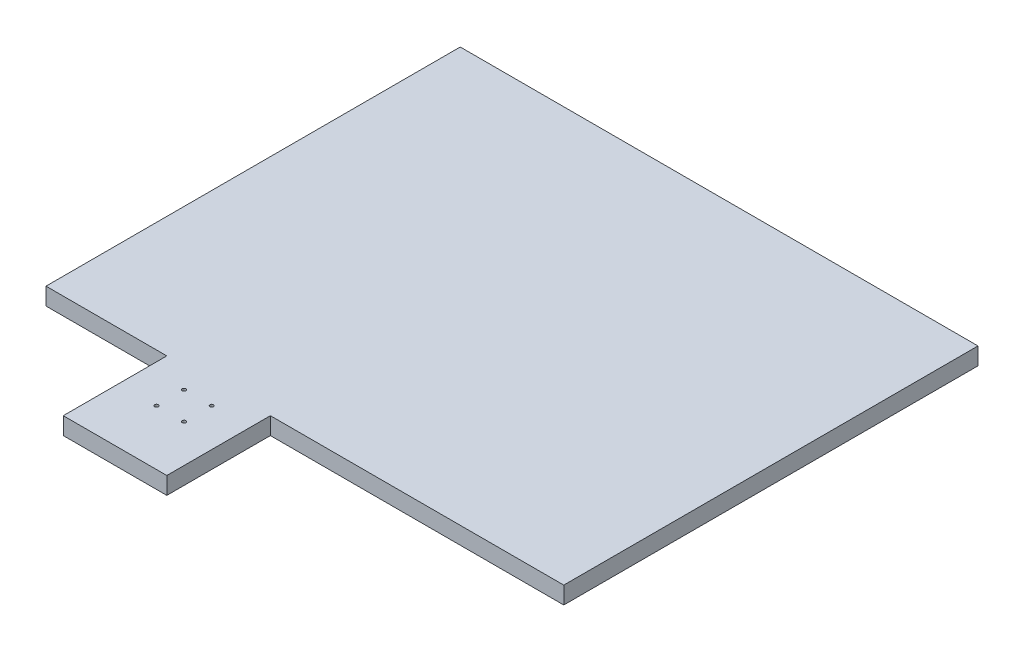
SolidWorks part; units mm, degrees
ref_plane "前基準面" through (0, 0, 0) normal (0, 0, 1) x (1, 0, 0)
ref_plane "上基準面" through (0, 0, 0) normal (0, 1, 0) x (1, 0, 0)
ref_plane "右基準面" through (0, 0, 0) normal (1, 0, 0) x (0, 0, -1)
sketch "草圖1" plane through (0, 0, 0) normal (0, 1, 0) x (1, 0, 0)
  line L0 (-50, -987.0204) -> (-50, 49012.9796) construction
  line L1 (-150, -120) -> (-80, -120)
  line L2 (-150, -120) -> (-150, 120)
  line L3 (-150, 120) -> (150, 120)
  line L4 (150, -120) -> (150, 120)
  line L5 (-150, -120) -> (150, 120) construction
  line L6 (-150, 120) -> (150, -120) construction
  line L7 (-80, -120) -> (-80, -180)
  line L8 (-80, -180) -> (-20, -180)
  line L9 (-20, -180) -> (-20, -120)
  line L10 (-20, -120) -> (150, -120)
  point P0 (0, 0)
  point P10 (-50, -180)
  dimension "D1" = 300
  dimension "D2" = 240
  dimension "D3" = 200
  dimension "D4" = 60
  dimension "D5" = 60
extrude "填料-伸長1" add sketch "草圖1" along normal blind 10
sketch "草圖2" plane through (0, 0, 0) normal (0, -1, 0) x (1, 0, 0)
  line L0 (-50, -820) -> (-50, 49180) construction
  line L1 (-80, 180) -> (-20, 180) construction
  line L2 (-1080, 140) -> (48920, 140) construction
  line L3 (-80, 120) -> (-80, 180) construction
  line L4 (-150, 120) -> (-80, 120) construction
  line L6 (-40, 150) -> (-60, 150)
  line L7 (-40, 150) -> (-40, 130)
  line L8 (-40, 130) -> (-60, 130)
  line L9 (-60, 150) -> (-60, 130)
  line L10 (-40, 150) -> (-60, 130) construction
  line L11 (-40, 130) -> (-60, 150) construction
  circle A0 centre (-58, 132) radius 1.05
  circle A1 centre (-58, 148) radius 1.05
  circle A2 centre (-42, 148) radius 1.05
  circle A3 centre (-42, 132) radius 1.05
  point P5 (-50, 180)
  point P20 (-50, 140)
  dimension "D1" = 2.1
  dimension "D2" = 20
  dimension "D3" = 8
  dimension "D4" = 8
  dimension "D5" = 20
  dimension "D6" = 20
extrude "除料-伸長2" cut sketch "草圖2" against normal blind 8 contours L6 L9 L8 L7 A1 A0 A2 A3 region at (-50, 0, 140)
extrude "除料-伸長3" cut sketch "草圖2<3>" against normal through all contours A3 | A0 | A1 | A2 region at (-58, 0, 132) region at (-58, 0, 148) region at (-42, 0, 148) region at (-42, 0, 132)
sketch "草圖2<3>" plane through (0, 0, 0) normal (0, -1, 0) x (1, 0, 0) same geometry as "草圖2"
